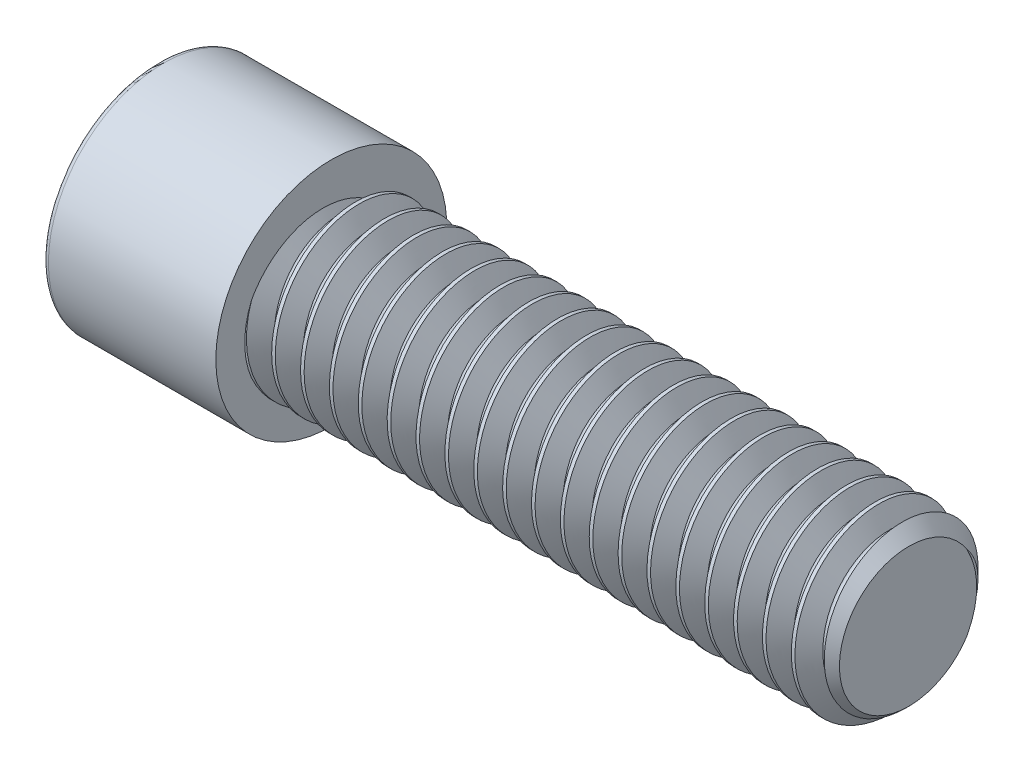
SolidWorks part; units mm, degrees
ref_plane "Ebene vorne" through (0, 0, 0) normal (0, 0, 1) x (1, 0, 0)
ref_plane "Ebene oben" through (0, 0, 0) normal (0, 1, 0) x (1, 0, 0)
ref_plane "Ebene rechts" through (0, 0, 0) normal (1, 0, 0) x (0, 0, -1)
sketch "Sketch1" plane through (0, 0, 0) normal (0, 0, 1) x (1, 0, 0)
  line L0 (-14.6254, 0) -> (16.6081, 0) construction
  line L1 (0, 0) -> (0, 2)
  line L2 (0, 2) -> (3, 2)
  line L3 (3, 2) -> (3, 1.5)
  line L4 (3, 1.5) -> (13, 1.5)
  line L5 (13, 1.5) -> (13, 0)
  line L6 (0, 0) -> (13, 0)
  dimension "D1" = 1.5
  dimension "D2" = 10
  dimension "D3" = 2
  dimension "D4" = 3
other "AlignGroup1"
other "AlignGroup2"
other "AlignGroup3"
revolve "Revolve1" add sketch "Sketch1" angle 360 about L0
sketch "Sketch3" plane through (3, 0, 0) normal (1, 0, 0) x (0, 0, -1)
  circle A0 centre (0, 0) radius 1.5
curve "Helix/Spiral1" pitch 0.5 height 11 turns 22
sketch "Sketch4" plane through (0, 0, 0) normal (0, 1, 0) x (1, 0, 0)
  line L0 (-6.0413, 0) -> (11.0618, 0) construction
  line L1 (-6.0413, 1.5) -> (11.0618, 1.5) construction
  dimension "D1" = 1.5
chamfer "Chamfer1" distance 0.3 angle 45 1 edges at (13, 0, 1.5)
sketch "Sketch5" plane through (0, 0, 0) normal (0, 1, 0) x (1, 0, 0)
  line L0 (4.5877, 1.3375) -> (3.435, 1.3375) construction
  line L1 (-6.0413, 0) -> (11.0618, 0) construction
  line L2 (2.75, 1.6191) -> (2.75, 0.9933) construction
  line L3 (2.5, 1.5889) -> (2.5, 0.9756) construction
  line L4 (2.7812, 1.5) -> (2.9582, 1.1935)
  line L5 (2.7188, 1.5) -> (2.5418, 1.1935)
  line L6 (-6.0413, 1.5) -> (11.0618, 1.5) construction
  line L7 (3.6285, 1.1935) -> (3.4482, 1.1935) construction
  line L8 (3, 1.5889) -> (3, 0.9756) construction
  line L9 (2.7188, 1.5) -> (2.7812, 1.5)
  line L10 (2.5, 1.1774) -> (3.2169, 1.1774)
  line L11 (2.75, 1.5541) -> (3, 1.1211) construction
  line L13 (2.75, 1.5541) -> (2.5, 1.1208) construction
  line L14 (3, -2) -> (3, 2) construction
  line L15 (3.2188, 1.5) -> (3.0418, 1.1935)
  line L16 (2.7812, 1.5) -> (3.2188, 1.5)
  arc A1 (2.9582, 1.1935) -> (3.0418, 1.1935) centre (3, 1.2395) ccw
  arc A2 (2.5418, 1.1935) -> (2.5, 1.1774) centre (2.5, 1.2395) cw
  spline S0 degree 3 poles (3, 1.5) (3.0104, 1.5) (3.0313, 1.4219) (3.0625, 1.0883) (3.1042, 0.4225) (3.1458, -0.4225) (3.1875, -1.0883) (3.2188, -1.4219) (3.25, -1.5391) (3.2813, -1.4219) (3.3125, -1.0883) (3.3542, -0.4225) (3.3958, 0.4225) (3.4375, 1.0883) (3.4688, 1.4219) (3.5, 1.5391) (3.5313, 1.4219) (3.5625, 1.0883) (3.6042, 0.4225) (3.6458, -0.4225) (3.6875, -1.0883) (3.7188, -1.4219) (3.75, -1.5391) (3.7812, -1.4219) (3.8125, -1.0883) (3.8542, -0.4225) (3.8958, 0.4225) (3.9375, 1.0883) (3.9688, 1.4219) (4, 1.5391) (4.0313, 1.4219) (4.0625, 1.0883) (4.1042, 0.4225) (4.1458, -0.4225) (4.1875, -1.0883) (4.2188, -1.4219) (4.25, -1.5391) (4.2813, -1.4219) (4.3125, -1.0883) (4.3542, -0.4225) (4.3958, 0.4225) (4.4375, 1.0883) (4.4688, 1.4219) (4.5, 1.5391) (4.5313, 1.4219) (4.5625, 1.0883) (4.6042, 0.4225) (4.6458, -0.4225) (4.6875, -1.0883) (4.7188, -1.4219) (4.75, -1.5391) (4.7813, -1.4219) (4.8125, -1.0883) (4.8542, -0.4225) (4.8958, 0.4225) (4.9375, 1.0883) (4.9688, 1.4219) (5, 1.5391) (5.0313, 1.4219) (5.0625, 1.0883) (5.1042, 0.4225) (5.1458, -0.4225) (5.1875, -1.0883) (5.2188, -1.4219) (5.25, -1.5391) (5.2813, -1.4219) (5.3125, -1.0883) (5.3542, -0.4225) (5.3958, 0.4225) (5.4375, 1.0883) (5.4688, 1.4219) (5.5, 1.5391) (5.5313, 1.4219) (5.5625, 1.0883) (5.6042, 0.4225) (5.6458, -0.4225) (5.6875, -1.0883) (5.7188, -1.4219) (5.75, -1.5391) (5.7813, -1.4219) (5.8125, -1.0883) (5.8542, -0.4225) (5.8958, 0.4225) (5.9375, 1.0883) (5.9688, 1.4219) (6, 1.5391) (6.0313, 1.4219) (6.0625, 1.0883) (6.1042, 0.4225) (6.1458, -0.4225) (6.1875, -1.0883) (6.2188, -1.4219) (6.25, -1.5391) (6.2812, -1.4219) (6.3125, -1.0883) (6.3542, -0.4225) (6.3958, 0.4225) (6.4375, 1.0883) (6.4688, 1.4219) (6.5, 1.5391) (6.5313, 1.4219) (6.5625, 1.0883) (6.6042, 0.4225) (6.6458, -0.4225) (6.6875, -1.0883) (6.7188, -1.4219) (6.75, -1.5391) (6.7813, -1.4219) (6.8125, -1.0883) (6.8542, -0.4225) (6.8958, 0.4225) (6.9375, 1.0883) (6.9688, 1.4219) (7, 1.5391) (7.0313, 1.4219) (7.0625, 1.0883) (7.1042, 0.4225) (7.1458, -0.4225) (7.1875, -1.0883) (7.2188, -1.4219) (7.25, -1.5391) (7.2813, -1.4219) (7.3125, -1.0883) (7.3542, -0.4225) (7.3958, 0.4225) (7.4375, 1.0883) (7.4688, 1.4219) (7.5, 1.5391) (7.5313, 1.4219) (7.5625, 1.0883) (7.6042, 0.4225) (7.6458, -0.4225) (7.6875, -1.0883) (7.7188, -1.4219) (7.75, -1.5391) (7.7813, -1.4219) (7.8125, -1.0883) (7.8542, -0.4225) (7.8958, 0.4225) (7.9375, 1.0883) (7.9688, 1.4219) (8, 1.5391) (8.0313, 1.4219) (8.0625, 1.0883) (8.1042, 0.4225) (8.1458, -0.4225) (8.1875, -1.0883) (8.2188, -1.4219) (8.25, -1.5391) (8.2813, -1.4219) (8.3125, -1.0883) (8.3542, -0.4225) (8.3958, 0.4225) (8.4375, 1.0883) (8.4688, 1.4219) (8.5, 1.5391) (8.5313, 1.4219) (8.5625, 1.0883) (8.6042, 0.4225) (8.6458, -0.4225) (8.6875, -1.0883) (8.7188, -1.4219) (8.75, -1.5391) (8.7813, -1.4219) (8.8125, -1.0883) (8.8542, -0.4225) (8.8958, 0.4225) (8.9375, 1.0883) (8.9688, 1.4219) (9, 1.5391) (9.0313, 1.4219) (9.0625, 1.0883) (9.1042, 0.4225) (9.1458, -0.4225) (9.1875, -1.0883) (9.2188, -1.4219) (9.25, -1.5391) (9.2813, -1.4219) (9.3125, -1.0883) (9.3542, -0.4225) (9.3958, 0.4225) (9.4375, 1.0883) (9.4688, 1.4219) (9.5, 1.5391) (9.5313, 1.4219) (9.5625, 1.0883) (9.6042, 0.4225) (9.6458, -0.4225) (9.6875, -1.0883) (9.7188, -1.4219) (9.75, -1.5391) (9.7813, -1.4219) (9.8125, -1.0883) (9.8542, -0.4225) (9.8958, 0.4225) (9.9375, 1.0883) (9.9688, 1.4219) (10, 1.5391) (10.0313, 1.4219) (10.0625, 1.0883) (10.1042, 0.4225) (10.1458, -0.4225) (10.1875, -1.0883) (10.2188, -1.4219) (10.25, -1.5391) (10.2813, -1.4219) (10.3125, -1.0883) (10.3542, -0.4225) (10.3958, 0.4225) (10.4375, 1.0883) (10.4688, 1.4219) (10.5, 1.5391) (10.5313, 1.4219) (10.5625, 1.0883) (10.6042, 0.4225) (10.6458, -0.4225) (10.6875, -1.0883) (10.7188, -1.4219) (10.75, -1.5391) (10.7813, -1.4219) (10.8125, -1.0883) (10.8542, -0.4225) (10.8958, 0.4225) (10.9375, 1.0883) (10.9688, 1.4219) (11, 1.5391) (11.0313, 1.4219) (11.0625, 1.0883) (11.1042, 0.4225) (11.1458, -0.4225) (11.1875, -1.0883) (11.2188, -1.4219) (11.25, -1.5391) (11.2813, -1.4219) (11.3125, -1.0883) (11.3542, -0.4225) (11.3958, 0.4225) (11.4375, 1.0883) (11.4688, 1.4219) (11.5, 1.5391) (11.5313, 1.4219) (11.5625, 1.0883) (11.6042, 0.4225) (11.6458, -0.4225) (11.6875, -1.0883) (11.7188, -1.4219) (11.75, -1.5391) (11.7813, -1.4219) (11.8125, -1.0883) (11.8542, -0.4225) (11.8958, 0.4225) (11.9375, 1.0883) (11.9688, 1.4219) (12, 1.5391) (12.0313, 1.4219) (12.0625, 1.0883) (12.1042, 0.4225) (12.1458, -0.4225) (12.1875, -1.0883) (12.2188, -1.4219) (12.25, -1.5391) (12.2813, -1.4219) (12.3125, -1.0883) (12.3542, -0.4225) (12.3958, 0.4225) (12.4375, 1.0883) (12.4688, 1.4219) (12.5, 1.5391) (12.5313, 1.4219) (12.5625, 1.0883) (12.6042, 0.4225) (12.6458, -0.4225) (12.6875, -1.0883) (12.7188, -1.4219) (12.75, -1.5391) (12.7813, -1.4219) (12.8125, -1.0883) (12.8542, -0.4225) (12.8958, 0.4225) (12.9375, 1.0883) (12.9688, 1.4219) (13, 1.5391) (13.0313, 1.4219) (13.0625, 1.0883) (13.1042, 0.4225) (13.1458, -0.4225) (13.1875, -1.0883) (13.2188, -1.4219) (13.25, -1.5391) (13.2813, -1.4219) (13.3125, -1.0883) (13.3542, -0.4225) (13.3958, 0.4225) (13.4375, 1.0883) (13.4687, 1.4219) (13.5, 1.5391) (13.5312, 1.4219) (13.5625, 1.0883) (13.6042, 0.4225) (13.6458, -0.4225) (13.6875, -1.0883) (13.7187, -1.4219) (13.75, -1.5391) (13.7812, -1.4219) (13.8125, -1.0883) (13.8542, -0.4225) (13.8958, 0.4225) (13.9375, 1.0883) (13.9687, 1.4219) (13.9896, 1.5) (14, 1.5) knots 0 0 0 0 0.002841 0.005682 0.008523 0.014205 0.017045 0.019886 0.022727 0.025568 0.028409 0.03125 0.036932 0.039773 0.042614 0.045455 0.048295 0.051136 0.053977 0.059659 0.0625 0.065341 0.068182 0.071023 0.073864 0.076705 0.082386 0.085227 0.088068 0.090909 0.09375 0.096591 0.099432 0.105114 0.107955 0.110795 0.113636 0.116477 0.119318 0.122159 0.127841 0.130682 0.133523 0.136364 0.139205 0.142045 0.144886 0.150568 0.153409 0.15625 0.159091 0.161932 0.164773 0.167614 0.173295 0.176136 0.178977 0.181818 0.184659 0.1875 0.190341 0.196023 0.198864 0.201705 0.204545 0.207386 0.210227 0.213068 0.21875 0.221591 0.224432 0.227273 0.230114 0.232955 0.235795 0.241477 0.244318 0.247159 0.25 0.252841 0.255682 0.258523 0.264205 0.267045 0.269886 0.272727 0.275568 0.278409 0.28125 0.286932 0.289773 0.292614 0.295455 0.298295 0.301136 0.303977 0.309659 0.3125 0.315341 0.318182 0.321023 0.323864 0.326705 0.332386 0.335227 0.338068 0.340909 0.34375 0.346591 0.349432 0.355114 0.357955 0.360795 0.363636 0.366477 0.369318 0.372159 0.377841 0.380682 0.383523 0.386364 0.389205 0.392045 0.394886 0.400568 0.403409 0.40625 0.409091 0.411932 0.414773 0.417614 0.423295 0.426136 0.428977 0.431818 0.434659 0.4375 0.440341 0.446023 0.448864 0.451705 0.454545 0.457386 0.460227 0.463068 0.46875 0.471591 0.474432 0.477273 0.480114 0.482955 0.485795 0.491477 0.494318 0.497159 0.5 0.502841 0.505682 0.508523 0.514205 0.517045 0.519886 0.522727 0.525568 0.528409 0.53125 0.536932 0.539773 0.542614 0.545455 0.548295 0.551136 0.553977 0.559659 0.5625 0.565341 0.568182 0.571023 0.573864 0.576705 0.582386 0.585227 0.588068 0.590909 0.59375 0.596591 0.599432 0.605114 0.607955 0.610795 0.613636 0.616477 0.619318 0.622159 0.627841 0.630682 0.633523 0.636364 0.639205 0.642045 0.644886 0.650568 0.653409 0.65625 0.659091 0.661932 0.664773 0.667614 0.673295 0.676136 0.678977 0.681818 0.684659 0.6875 0.690341 0.696023 0.698864 0.701705 0.704545 0.707386 0.710227 0.713068 0.71875 0.721591 0.724432 0.727273 0.730114 0.732955 0.735795 0.741477 0.744318 0.747159 0.75 0.752841 0.755682 0.758523 0.764205 0.767045 0.769886 0.772727 0.775568 0.778409 0.78125 0.786932 0.789773 0.792614 0.795455 0.798295 0.801136 0.803977 0.809659 0.8125 0.815341 0.818182 0.821023 0.823864 0.826705 0.832386 0.835227 0.838068 0.840909 0.84375 0.846591 0.849432 0.855114 0.857955 0.860795 0.863636 0.866477 0.869318 0.872159 0.877841 0.880682 0.883523 0.886364 0.889205 0.892045 0.894886 0.900568 0.903409 0.90625 0.909091 0.911932 0.914773 0.917614 0.923295 0.926136 0.928977 0.931818 0.934659 0.9375 0.940341 0.946023 0.948864 0.951705 0.954545 0.957386 0.960227 0.963068 0.96875 0.971591 0.974432 0.977273 0.980114 0.982955 0.985795 0.991477 0.994318 0.997159 1 1 1 1 construction
  point P12 (0, 0)
  dimension "D8" = 0
  dimension "D2" = 0.5
  dimension "D4" = 0.0541
  dimension "D6" = 0.0161
  dimension "D1" = 1.3375
  dimension "D3" = 60
  dimension "D5" = 0.25
  dimension "D7" = 1.1935
sweep "Cut-Sweep2" cut profiles "Sketch5" path "Helix/Spiral1"
sketch "Sketch6" plane through (0, 0, 0) normal (-1, 0, 0) x (0, 0, 1)
  line L0 (0.5774, 1) -> (-0.5774, 1)
  line L1 (-0.5774, 1) -> (-1.1547, 0)
  line L2 (-1.1547, 0) -> (-0.5774, -1)
  line L3 (-0.5774, -1) -> (0.5774, -1)
  line L4 (0.5774, -1) -> (1.1547, 0)
  line L5 (1.1547, 0) -> (0.5774, 1)
  line L6 (-0.5774, -1) -> (0.5774, 1) construction
  line L7 (-0.5774, 1) -> (0.5774, -1) construction
  point P6 (0, 0)
  dimension "D1" = 2
  dimension "D2" = 2
  dimension "D3" = 0
  dimension "D4" = 2
extrude "Cut-Extrude1" cut sketch "Sketch6" against normal blind 1.5
chamfer "Chamfer2" distance 0.1 angle 45 6 edges at (0, 0.5, -0.866) (0, -0.5, -0.866) (0, -1, 0) (0, -0.5, 0.866) (0, 0.5, 0.866) (0, 1, 0)
fillet "Fillet1" radius 0.1 1 edges at (0, 0, 2)
